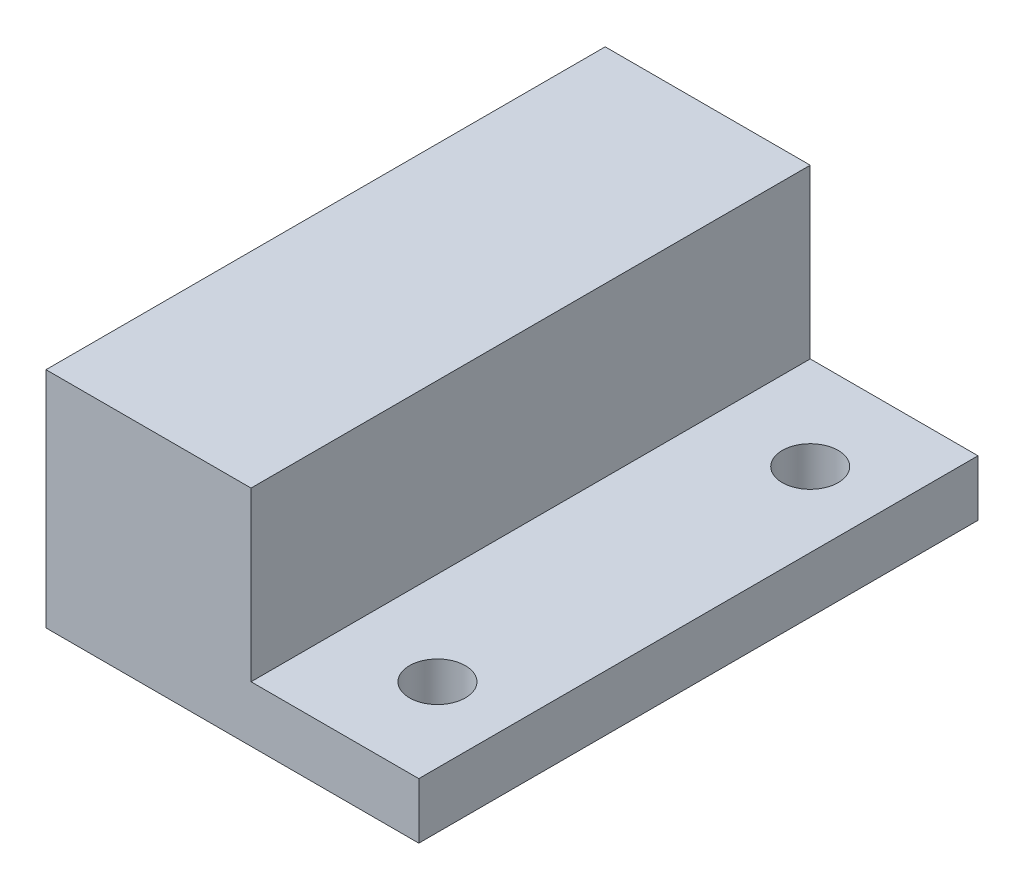
SolidWorks part; units mm, degrees
ref_plane "Front Plane" through (0, 0, 0) normal (0, 0, 1) x (1, 0, 0)
ref_plane "Top Plane" through (0, 0, 0) normal (0, 1, 0) x (1, 0, 0)
ref_plane "Right Plane" through (0, 0, 0) normal (1, 0, 0) x (0, 0, -1)
sketch "Sketch1" plane through (0, 0, 0) normal (0, 1, 0) x (1, 0, 0)
  line L0 (0, 0) -> (0, -25.4) construction
  line L1 (-20.32, 6.35) -> (5.08, 6.35)
  line L2 (-20.32, 6.35) -> (-20.32, -31.75)
  line L3 (-20.32, -31.75) -> (5.08, -31.75)
  line L4 (5.08, 6.35) -> (5.08, -31.75)
  circle A0 centre (0, 0) radius 1.905
  circle A1 centre (0, -25.4) radius 1.905
  point P6 (-20.32, -12.7)
  point P11 (0, 0)
  point P12 (0, -12.7)
  point P13 (0, 0)
  dimension "D1" = 25.4
  dimension "D2" = 3.81
  dimension "D3" = 3.81
  dimension "D4" = 5.08
  dimension "D5" = 38.1
  dimension "D6" = 25.4
extrude "Boss-Extrude1" add sketch "Sketch1" along normal blind 3.81
sketch "Sketch2" plane through (0, 3.81, 0) normal (0, 1, 0) x (1, 0, 0)
  line L0 (-20.32, 6.35) -> (-20.32, -31.75)
  line L1 (-20.32, -31.75) -> (-6.35, -31.75)
  line L2 (-20.32, -31.75) -> (5.08, -31.75) construction
  line L3 (-6.35, -31.75) -> (-6.35, 6.35)
  line L4 (5.08, 6.35) -> (-20.32, 6.35) construction
  line L5 (-6.35, 6.35) -> (-8.89, 6.35)
  line L6 (-8.89, 6.35) -> (-8.89, -29.21)
  line L7 (-8.89, -29.21) -> (-17.78, -29.21)
  line L8 (-17.78, -29.21) -> (-17.78, 6.35)
  line L9 (-17.78, 6.35) -> (-20.32, 6.35)
  dimension "D1" = 2.54
  dimension "D2" = 8.89
  dimension "D3" = 2.54
extrude "Boss-Extrude2" add sketch "Sketch2" along normal blind 8.89 contours L0 L1 L3 L5 L6 L7 L8 L9
sketch "Sketch3" plane through (0, 12.7, 0) normal (0, 1, 0) x (1, 0, 0)
  line L1 (-20.32, 6.35) -> (-6.35, 6.35)
  line L2 (-20.32, 6.35) -> (-20.32, -31.75)
  line L3 (-20.32, -31.75) -> (-6.35, -31.75)
  line L4 (-6.35, 6.35) -> (-6.35, -31.75)
extrude "Boss-Extrude3" add sketch "Sketch3" along normal blind 2.54
chamfer "Chamfer1" distance 1.27 angle 45 2 edges at (-8.89, 12.7, 11.43) (-17.78, 12.7, 11.43)
